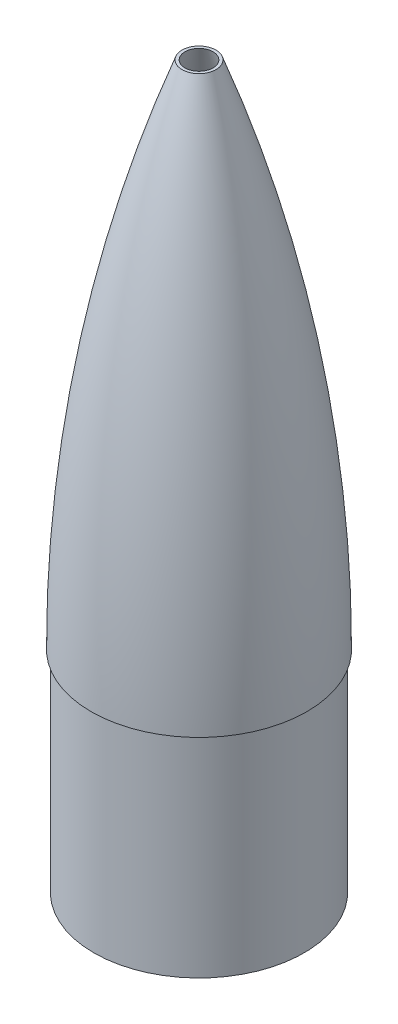
SolidWorks part; units mm, degrees
other "Markup1"
sketch "Sketch4" plane through (78.16, -154.2442, 78.16) normal (0.9651, -0.1718, 0.1975) x (-0.1686, -0.9851, -0.0334)
material "Thornel Mat VMA"
ref_plane "Front Plane" through (0, 0, 0) normal (0, 0, 1) x (1, 0, 0)
ref_plane "Top Plane" through (0, 0, 0) normal (0, 1, 0) x (1, 0, 0)
ref_plane "Right Plane" through (0, 0, 0) normal (1, 0, 0) x (0, 0, -1)
sketch "Sketch1" plane through (0, 0, 0) normal (0, 0, 1) x (1, 0, 0)
  line L3 (0, 0) -> (0, 398.8705) construction
  line L6 (0, 400) -> (0, 401.8534)
  line L8 (78.2, 0) -> (76.2, 0)
  line L9 (0, 400) -> (0, 396.4892)
  line L10 (76.2, 0) -> (-993.4203, 0) construction
  line L11 (0, 411.0234) -> (0, 614.1078) construction
  arc A0 (76.2, 0) -> (0, 396.4892) centre (-993.4203, 0) ccw
  arc A1 (78.2, 0) -> (0, 401.8534) centre (-993.4203, 0) ccw
  circle A2 centre (-993.4203, 0) radius 1069.6203 construction
  circle A3 centre (-993.4203, 0) radius 1071.6203 construction
  point P11 (0, 400)
  dimension "D1" = 400
  dimension "D2" = 3.5108
  dimension "D3" = 2
  dimension "D4" = 76.2
revolve "Revolve3" add sketch "Sketch1" angle 360 about L6 reverse direction yes
sketch "Sketch2" plane through (0, 0, 0) normal (0, 1, 0) x (1, 0, 0)
  circle A3 centre (0, 0) radius 76.2 construction
  circle A4 centre (0, 0) radius 76.2
  circle A5 centre (0, 0) radius 74.2
  dimension "D1" = 2
extrude "Boss-Extrude1" add sketch "Sketch2" against normal blind 152.4 and the other way blind 10
ref_plane "Plane2" through (0, 400, 0) normal (0, -1, 0) x (-1, 0, 0)
ref_plane "Plane4" through (0, 370, 0) normal (0, -1, 0) x (-1, 0, 0)
sketch "Sketch6" plane through (0, 370, 0) normal (0, -1, 0) x (-1, 0, 0)
  circle A0 centre (0, 0) radius 45.0274
extrude "Cut-Extrude1" cut sketch "Sketch6" against normal blind 40
ref_plane "Plane3" through (0, -6.4, 0) normal (0, -1, 0) x (-1, 0, 0)
sketch "Sketch5" plane through (0, -6.4, 0) normal (0, -1, 0) x (-1, 0, 0)
  circle A0 centre (0, 0) radius 74.2
  circle A1 centre (0, 0) radius 74.2
